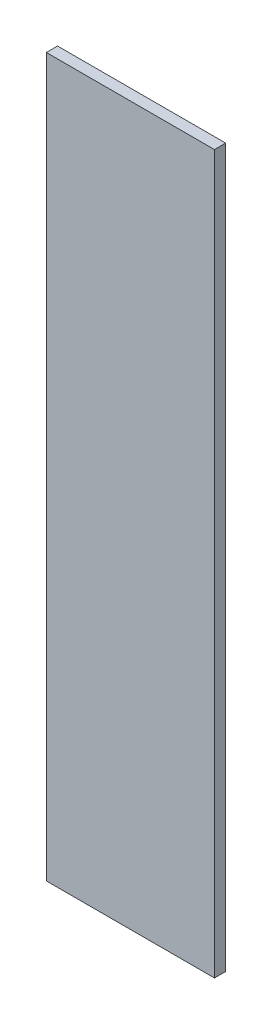
SolidWorks part; units mm, degrees
ref_plane "Front Plane" through (0, 0, 0) normal (0, 0, 1) x (1, 0, 0)
ref_plane "Top Plane" through (0, 0, 0) normal (0, 1, 0) x (1, 0, 0)
ref_plane "Right Plane" through (0, 0, 0) normal (1, 0, 0) x (0, 0, -1)
sketch "Sketch1" plane through (0, 0, 0) normal (0, 0, 1) x (1, 0, 0)
  line L1 (-37.5, -160) -> (37.5, -160)
  line L2 (-37.5, -160) -> (-37.5, 160)
  line L3 (-37.5, 160) -> (37.5, 160)
  line L4 (37.5, -160) -> (37.5, 160)
  line L5 (-37.5, -160) -> (37.5, 160) construction
  line L6 (-37.5, 160) -> (37.5, -160) construction
  point P0 (0, 0)
  dimension "D1" = 320
  dimension "D2" = 75
extrude "Boss-Extrude1" add sketch "Sketch1" along normal blind 5
